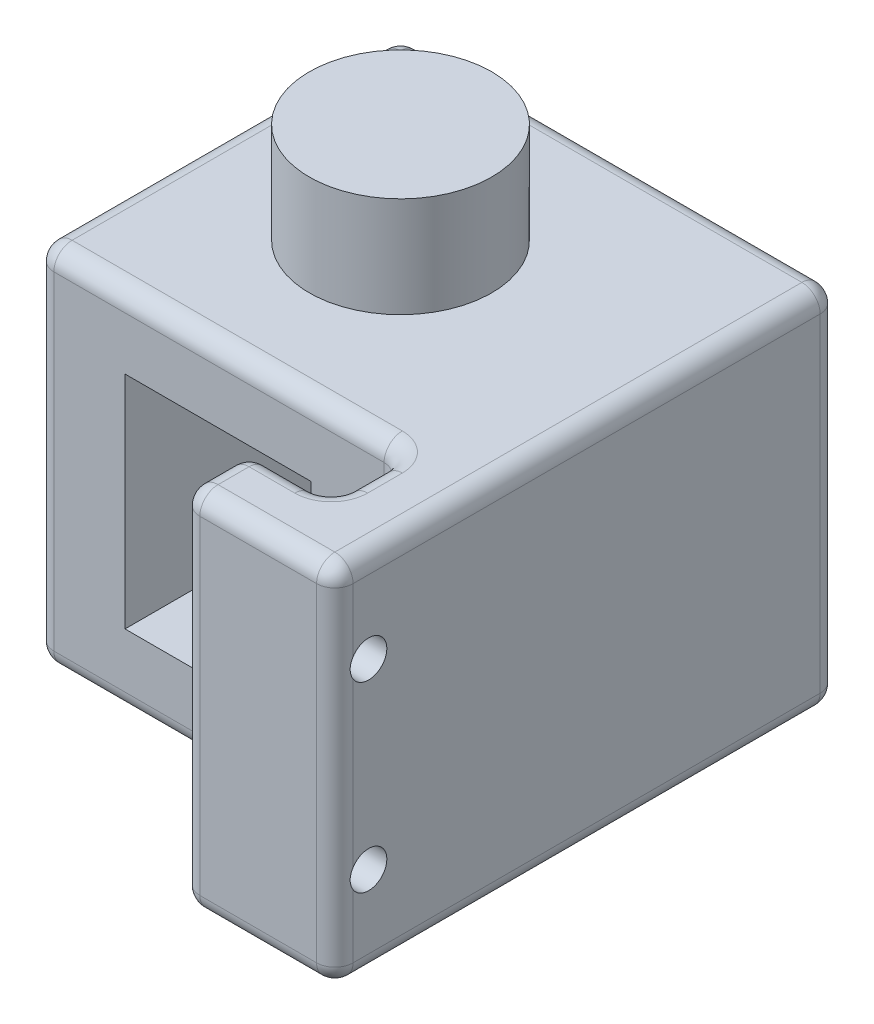
SolidWorks part; units mm, degrees
ref_plane "前视基准面" through (0, 0, 0) normal (0, 0, 1) x (1, 0, 0)
ref_plane "上视基准面" through (0, 0, 0) normal (0, 1, 0) x (1, 0, 0)
ref_plane "右视基准面" through (0, 0, 0) normal (1, 0, 0) x (0, 0, -1)
sketch "草图1" plane through (0, 0, 0) normal (0, 1, 0) x (1, 0, 0)
  line L0 (0, 0) -> (24, 0)
  line L1 (24, 0) -> (24, -27.6)
  line L2 (24, -27.6) -> (15.6, -27.6)
  line L3 (15.6, -27.6) -> (15.6, -23.9)
  line L4 (15.6, -23.9) -> (20.1, -23.9)
  line L5 (20.1, -23.9) -> (20.1, -20)
  line L6 (20.1, -20) -> (0, -20)
  line L7 (0, -20) -> (0, 0)
  dimension "D1" = 20
  dimension "D2" = 24
  dimension "D3" = 27.6
  dimension "D4" = 8.4
  dimension "D5" = 3.9
  dimension "D6" = 3.7
extrude "凸台-拉伸1" add sketch "草图1" along normal mid plane 20
sketch "草图3" plane through (0, 0, 0) normal (0, 1, 0) x (1, 0, 0)
  line L0 (24, 0) -> (0, 0) construction
  line L1 (0, 0) -> (0, -20) construction
  circle A0 centre (10, -10) radius 5
  dimension "D1" = 10
  dimension "D2" = 10
  dimension "D3" = 10
extrude "凸台-拉伸2" add sketch "草图3" along normal mid plane 31
sketch "草图2" plane through (0, 0, 0) normal (0, 0, -1) x (-1, 0, 0)
  line L0 (0, 10) -> (0, -10) construction
  line L1 (-15.1, 6.1) -> (-4.9, 6.1)
  line L2 (-15.1, 6.1) -> (-15.1, -6)
  line L3 (-15.1, -6) -> (-4.9, -6)
  line L4 (-4.9, 6.1) -> (-4.9, -6)
  line L5 (-24, -10) -> (0, -10) construction
  dimension "D1" = 10.2
  dimension "D2" = 12.1
  dimension "D3" = 4.9
  dimension "D4" = 4
extrude "切除-拉伸1" cut sketch "草图2" against normal through all
sketch "草图4" plane through (15.6, 0, 0) normal (-1, 0, 0) x (0, 0, 1)
  line L0 (25.75, 10) -> (25.75, -10) construction
  line L1 (23.9, 10) -> (27.6, 10) construction
  line L2 (23.9, -10) -> (27.6, -10) construction
  circle A0 centre (25.75, 5) radius 1
  circle A1 centre (25.75, -5) radius 1
  dimension "D1" = 2
  dimension "D2" = 5
  dimension "D3" = 5
extrude "切除-拉伸2" cut sketch "草图4" against normal through all
fillet "圆角1" radius 1 24 edges at (10.05, -10, 20) (20.1, -10, 21.95) (20.1, 10, 21.95) (17.85, -10, 23.9) (15.6, -10, 25.75) (19.8, -10, 27.6) (24, 0, 27.6) (15.6, 10, 25.75) (17.85, 10, 23.9) (19.8, 10, 27.6) (24, 10, 13.8) (24, 0, 0) (24, -10, 13.8) (12, -10, 0) (0, -10, 10) (12, 10, 0) (0, 0, 0) (0, 10, 10) (10.05, 10, 20) (0, 0, 20) (20.1, 0, 20) (20.1, 0, 23.9) (15.6, 0, 23.9) (15.6, 0, 27.6)
